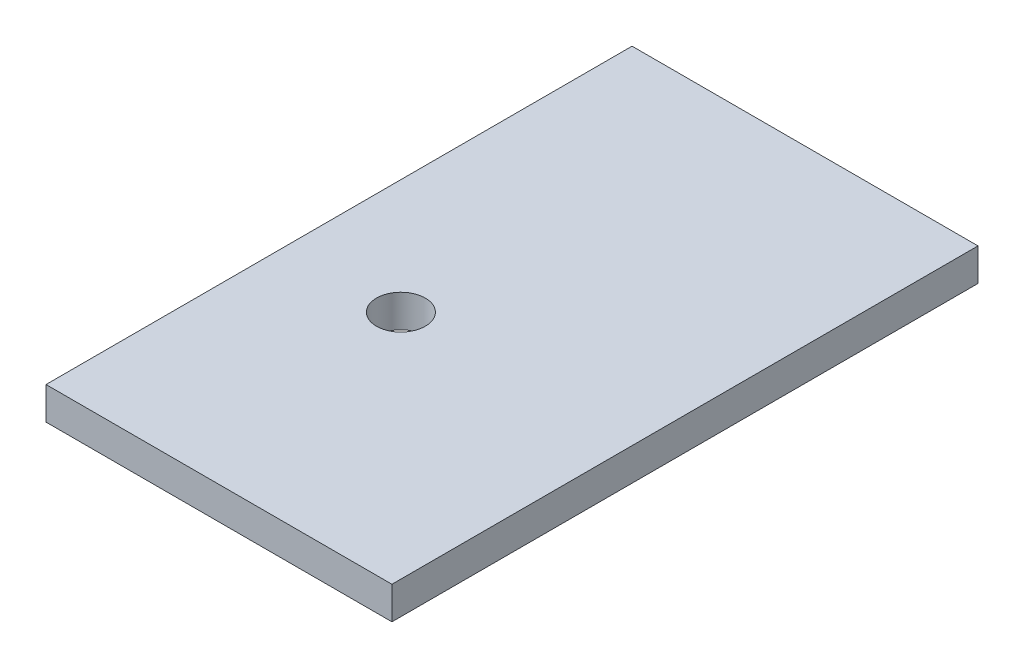
SolidWorks part; units mm, degrees
ref_plane "Front Plane" through (0, 0, 0) normal (0, 0, 1) x (1, 0, 0)
ref_plane "Top Plane" through (0, 0, 0) normal (0, 1, 0) x (1, 0, 0)
ref_plane "Right Plane" through (0, 0, 0) normal (1, 0, 0) x (0, 0, -1)
sketch "Sketch1" plane through (0, 0, 0) normal (0, 1, 0) x (1, 0, 0)
  line L1 (-21.25, 36) -> (21.25, 36)
  line L2 (-21.25, 36) -> (-21.25, -36)
  line L3 (-21.25, -36) -> (21.25, -36)
  line L4 (21.25, 36) -> (21.25, -36)
  circle A2 centre (-7.1496, -6.5) radius 3
  point P4 (0, 36)
  point P6 (-21.25, 0)
  dimension "D3" = 6
  dimension "D1" = 42.5
  dimension "D2" = 72
  dimension "D4" = 6.5
extrude "Boss-Extrude1" add sketch "Sketch1" along normal blind 4
equation "\"box_width\"=112"
equation "\"openable_top\"= 72"
equation "\"D1@Sketch1\"=\"wall\"+\"box_width\"-\"openable_top\""
equation "\"wall\" = 2.5"
equation "\"box_length\"= 67"
equation "\"D2@Sketch1\"=\"box_length\"+\"wall\"*2"
equation "\"D1@Boss-Extrude1\"=\"wall\""
